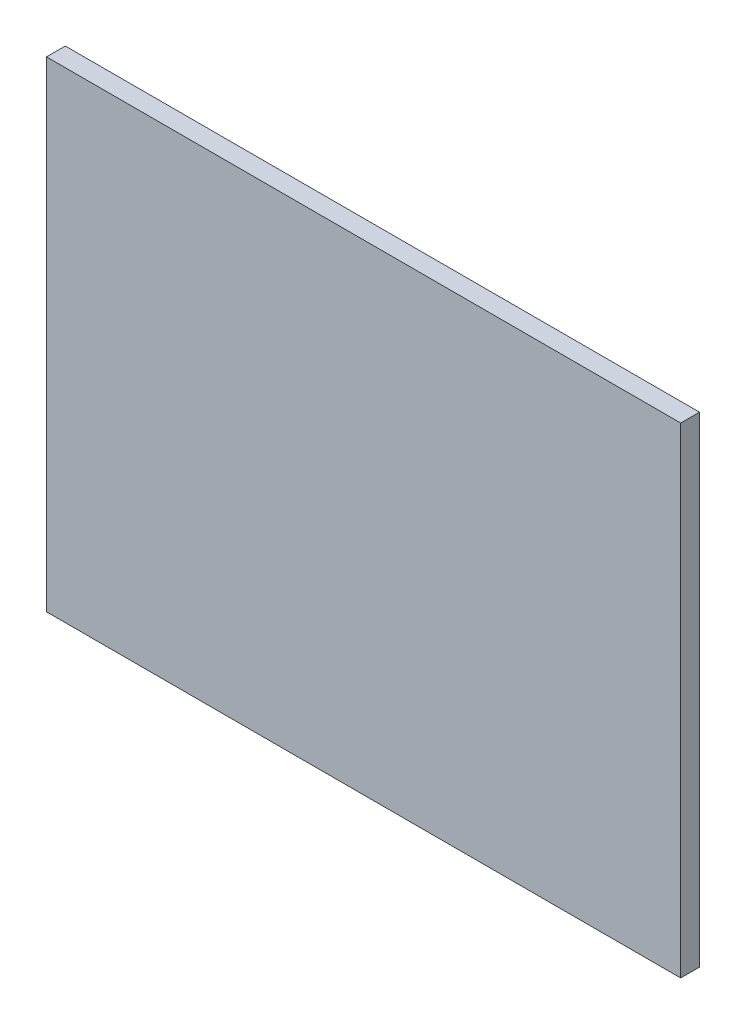
SolidWorks part; units mm, degrees
ref_plane "Front Plane" through (0, 0, 0) normal (0, 0, 1) x (1, 0, 0)
ref_plane "Top Plane" through (0, 0, 0) normal (0, 1, 0) x (1, 0, 0)
ref_plane "Right Plane" through (0, 0, 0) normal (1, 0, 0) x (0, 0, -1)
sketch "Sketch1" plane through (0, 0, 0) normal (0, 0, 1) x (1, 0, 0)
  line L1 (-48.8555, 21.6286) -> (15.1445, 21.6286)
  line L2 (-48.8555, 21.6286) -> (-48.8555, -26.8714)
  line L3 (-48.8555, -26.8714) -> (15.1445, -26.8714)
  line L4 (15.1445, 21.6286) -> (15.1445, -26.8714)
  dimension "D1" = 64
  dimension "D2" = 48.5
base flange "Base-Flange1" sketch "Sketch1" thickness 1.8974 reverse thickness direction no parameters "D1"=2.54
sketch "Bend-Lines1" plane through (0, 0, 0) normal (0, 1, 0) x (1, 0, 0)
sketch "Bounding-Box1" plane through (0, 0, 0) normal (0, 1, 0) x (1, 0, 0)
sheet metal parameters "Sheet-Metal1" thickness 1.8974 parameters "D1"=2.54
flat pattern "Flat-Pattern1" [suppressed]
sketch "Bend-Lines2" plane through (0, 0, 0) normal (0, 1, 0) x (1, 0, 0)
sketch "Bounding-Box2" [suppressed] plane through (0, 0, 0) normal (0, 1, 0) x (1, 0, 0)
